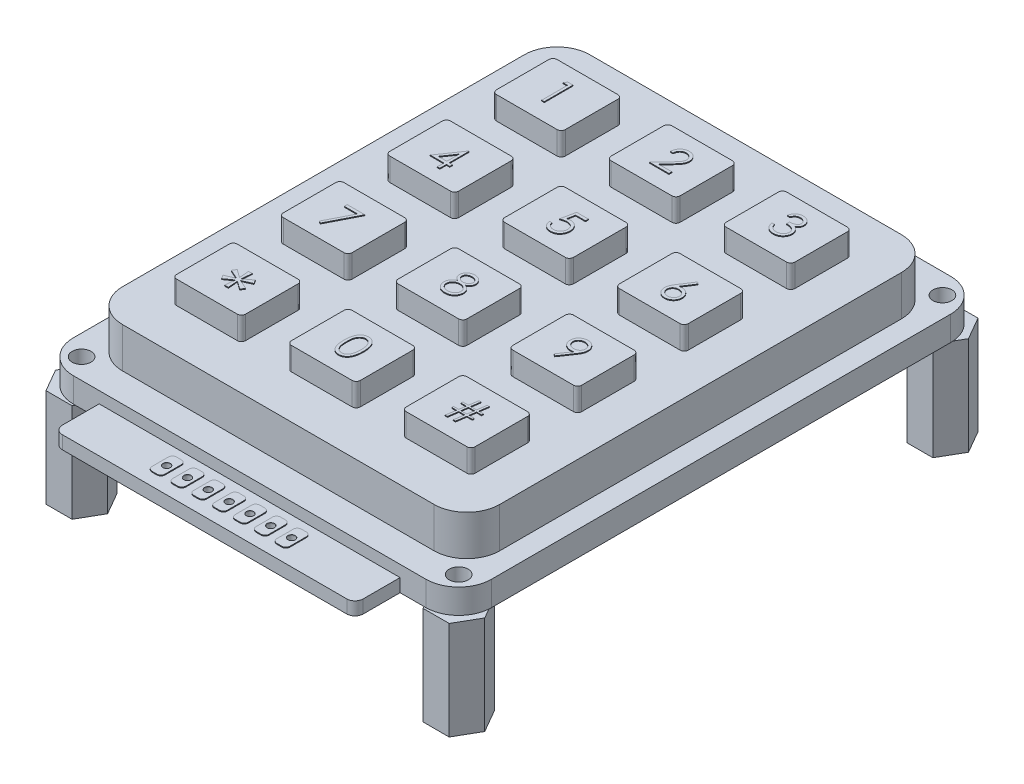
SolidWorks part; units mm, degrees
ref_plane "Front Plane" through (0, 0, 0) normal (0, 0, 1) x (1, 0, 0)
ref_plane "Top Plane" through (0, 0, 0) normal (0, 1, 0) x (1, 0, 0)
ref_plane "Right Plane" through (0, 0, 0) normal (1, 0, 0) x (0, 0, -1)
sketch "Sketch1" plane through (0, 0, 0) normal (0, 1, 0) x (1, 0, 0)
  line L0 (0, 71.2613) -> (0, -45.8043) construction
  line L1 (19.8246, -29.5) -> (21.4123, -32.25)
  line L2 (-19.8246, -29.5) -> (-21.4123, -26.75)
  line L3 (-21.4123, -26.75) -> (-24.5877, -26.75)
  line L4 (-24.5877, -26.75) -> (-26.1754, -29.5)
  line L5 (-26.1754, -29.5) -> (-24.5877, -32.25)
  line L6 (-24.5877, -32.25) -> (-21.4123, -32.25)
  line L7 (-21.4123, -32.25) -> (-19.8246, -29.5)
  line L8 (21.4123, -26.75) -> (19.8246, -29.5)
  line L9 (24.5877, -26.75) -> (21.4123, -26.75)
  line L10 (26.1754, -29.5) -> (24.5877, -26.75)
  line L11 (24.5877, -32.25) -> (26.1754, -29.5)
  line L12 (21.4123, -32.25) -> (24.5877, -32.25)
  line L13 (19.8246, 29.5) -> (21.4123, 26.75)
  line L14 (21.4123, 32.25) -> (19.8246, 29.5)
  line L15 (24.5877, 32.25) -> (21.4123, 32.25)
  line L16 (26.1754, 29.5) -> (24.5877, 32.25)
  line L17 (24.5877, 26.75) -> (26.1754, 29.5)
  line L18 (21.4123, 26.75) -> (24.5877, 26.75)
  line L19 (-26.1754, 29.5) -> (-24.5877, 26.75)
  line L20 (-24.5877, 32.25) -> (-26.1754, 29.5)
  line L21 (-21.4123, 32.25) -> (-24.5877, 32.25)
  line L22 (-19.8246, 29.5) -> (-21.4123, 32.25)
  line L23 (-21.4123, 26.75) -> (-19.8246, 29.5)
  line L24 (-24.5877, 26.75) -> (-21.4123, 26.75)
  circle A0 centre (-23, -29.5) radius 2.75 construction
  circle A1 centre (-23, -29.5) radius 1.5
  circle A2 centre (23, -29.5) radius 1.5
  circle A3 centre (23, 29.5) radius 1.5
  circle A4 centre (-23, 29.5) radius 1.5
  point P41 (0, 0)
  dimension "D1" = 29.5
  dimension "D3" = 2.75
  dimension "D4" = 3
  dimension "D10" = 29.5
  dimension "D11" = 23
  dimension "D5" = 5.5
  dimension "D2" = 23
  dimension "D6" = 2
  dimension "D7" = 2
  dimension "D8" = 29.5
  dimension "D9" = 46
extrude "Boss-Extrude1" add sketch "Sketch1" along normal blind 12
sketch "Sketch3" plane through (0, 12, 0) normal (0, 1, 0) x (1, 0, 0)
  line L1 (-21.5, -32) -> (21.5, -32)
  line L2 (-25.5, -28) -> (-25.5, 28)
  line L3 (-21.5, 32) -> (21.5, 32)
  line L4 (25.5, -28) -> (25.5, 28)
  line L5 (-25.5, -32) -> (25.5, 32) construction
  line L6 (-25.5, 32) -> (25.5, -32) construction
  circle A0 centre (-23, 29.5) radius 1.15
  circle A1 centre (23, 29.5) radius 1.15
  circle A2 centre (23, -29.5) radius 1.15
  circle A3 centre (-23, -29.5) radius 1.15
  arc A4 (-25.5, 28) -> (-21.5, 32) centre (-21.5, 28) cw
  arc A5 (21.5, 32) -> (25.5, 28) centre (21.5, 28) cw
  arc A6 (21.5, -32) -> (25.5, -28) centre (21.5, -28) ccw
  arc A7 (-21.5, -32) -> (-25.5, -28) centre (-21.5, -28) cw
  point P0 (0, 0)
  dimension "D3" = 2.3
  dimension "D10" = 4
  dimension "D11" = 4
  dimension "D12" = 4
  dimension "D13" = 4
  dimension "D1" = 64
  dimension "D2" = 51
  dimension "D6" = 46
  dimension "D7" = 59
  dimension "D8" = 29.5
  dimension "D9" = 23
  dimension "D4" = 2
  dimension "D5" = 2
extrude "Boss-Extrude3" add sketch "Sketch3" along normal blind 3 separate body
sketch "Sketch6" plane through (0, 15, 0) normal (0, 1, 0) x (1, 0, 0)
  line L1 (-19, -28.5) -> (19, -28.5)
  line L2 (-23, -24.5) -> (-23, 24.5)
  line L3 (-19, 28.5) -> (19, 28.5)
  line L4 (23, -24.5) -> (23, 24.5)
  line L5 (-23, -28.5) -> (23, 28.5) construction
  line L6 (-23, 28.5) -> (23, -28.5) construction
  arc A0 (-23, 24.5) -> (-19, 28.5) centre (-19, 24.5) cw
  arc A1 (-19, -28.5) -> (-23, -24.5) centre (-19, -24.5) cw
  arc A2 (19, -28.5) -> (23, -24.5) centre (19, -24.5) ccw
  arc A3 (19, 28.5) -> (23, 24.5) centre (19, 24.5) cw
  point P0 (0, 0)
  dimension "D3" = 4
  dimension "D4" = 4
  dimension "D5" = 4
  dimension "D6" = 4
  dimension "D1" = 57
  dimension "D2" = 46
extrude "Boss-Extrude4" add sketch "Sketch6" along normal blind 4.9 separate body
sketch "Sketch7" plane through (0, 19.9, 0) normal (0, 1, 0) x (1, 0, 0)
  line L0 (-3.7, -15.8) -> (3.7, -15.8)
  line L1 (-17.7, -23.2) -> (-10.3, -23.2)
  line L2 (-18.2, -22.7) -> (-18.2, -16.3)
  line L3 (-17.7, -15.8) -> (-10.3, -15.8)
  line L4 (-9.8, -22.7) -> (-9.8, -16.3)
  line L5 (-18.2, -23.2) -> (-9.8, -15.8) construction
  line L6 (-18.2, -15.8) -> (-9.8, -23.2) construction
  line L7 (-4.2, -22.7) -> (-4.2, -16.3)
  line L8 (-3.7, -23.2) -> (3.7, -23.2)
  line L9 (4.2, -22.7) -> (4.2, -16.3)
  line L10 (10.3, -15.8) -> (17.7, -15.8)
  line L11 (9.8, -22.7) -> (9.8, -16.3)
  line L12 (10.3, -23.2) -> (17.7, -23.2)
  line L13 (18.2, -22.7) -> (18.2, -16.3)
  line L14 (-3.7, -2.8) -> (3.7, -2.8)
  line L15 (-4.2, -9.7) -> (-4.2, -3.3)
  line L16 (-3.7, -10.2) -> (3.7, -10.2)
  line L17 (4.2, -9.7) -> (4.2, -3.3)
  line L18 (10.3, -2.8) -> (17.7, -2.8)
  line L19 (9.8, -9.7) -> (9.8, -3.3)
  line L20 (10.3, -10.2) -> (17.7, -10.2)
  line L21 (18.2, -9.7) -> (18.2, -3.3)
  line L22 (-3.7, 10.2) -> (3.7, 10.2)
  line L23 (-4.2, 3.3) -> (-4.2, 9.7)
  line L24 (-3.7, 2.8) -> (3.7, 2.8)
  line L25 (4.2, 3.3) -> (4.2, 9.7)
  line L26 (10.3, 10.2) -> (17.7, 10.2)
  line L27 (9.8, 3.3) -> (9.8, 9.7)
  line L28 (10.3, 2.8) -> (17.7, 2.8)
  line L29 (18.2, 3.3) -> (18.2, 9.7)
  line L30 (-3.7, 23.2) -> (3.7, 23.2)
  line L31 (-4.2, 16.3) -> (-4.2, 22.7)
  line L32 (-3.7, 15.8) -> (3.7, 15.8)
  line L33 (4.2, 16.3) -> (4.2, 22.7)
  line L34 (10.3, 23.2) -> (17.7, 23.2)
  line L35 (9.8, 16.3) -> (9.8, 22.7)
  line L36 (10.3, 15.8) -> (17.7, 15.8)
  line L37 (18.2, 16.3) -> (18.2, 22.7)
  line L38 (-17.7, -2.8) -> (-10.3, -2.8)
  line L39 (-18.2, -9.7) -> (-18.2, -3.3)
  line L40 (-17.7, -10.2) -> (-10.3, -10.2)
  line L41 (-9.8, -9.7) -> (-9.8, -3.3)
  line L42 (-17.7, 10.2) -> (-10.3, 10.2)
  line L43 (-18.2, 3.3) -> (-18.2, 9.7)
  line L44 (-17.7, 2.8) -> (-10.3, 2.8)
  line L45 (-9.8, 3.3) -> (-9.8, 9.7)
  line L46 (-17.7, 23.2) -> (-10.3, 23.2)
  line L47 (-18.2, 16.3) -> (-18.2, 22.7)
  line L48 (-17.7, 15.8) -> (-10.3, 15.8)
  line L49 (-9.8, 16.3) -> (-9.8, 22.7)
  arc A0 (-10.3, -23.2) -> (-9.8, -22.7) centre (-10.3, -22.7) ccw
  arc A1 (-10.3, -15.8) -> (-9.8, -16.3) centre (-10.3, -16.3) cw
  arc A2 (-18.2, -16.3) -> (-17.7, -15.8) centre (-17.7, -16.3) cw
  arc A3 (-17.7, -23.2) -> (-18.2, -22.7) centre (-17.7, -22.7) cw
  arc A4 (9.8, 16.3) -> (10.3, 15.8) centre (10.3, 16.3) ccw
  arc A5 (17.7, 15.8) -> (18.2, 16.3) centre (17.7, 16.3) ccw
  arc A6 (17.7, 23.2) -> (18.2, 22.7) centre (17.7, 22.7) cw
  arc A7 (10.3, 23.2) -> (9.8, 22.7) centre (10.3, 22.7) ccw
  arc A8 (-4.2, 16.3) -> (-3.7, 15.8) centre (-3.7, 16.3) ccw
  arc A9 (3.7, 15.8) -> (4.2, 16.3) centre (3.7, 16.3) ccw
  arc A10 (3.7, 23.2) -> (4.2, 22.7) centre (3.7, 22.7) cw
  arc A11 (-3.7, 23.2) -> (-4.2, 22.7) centre (-3.7, 22.7) ccw
  arc A12 (-18.2, 16.3) -> (-17.7, 15.8) centre (-17.7, 16.3) ccw
  arc A13 (-10.3, 15.8) -> (-9.8, 16.3) centre (-10.3, 16.3) ccw
  arc A14 (-10.3, 23.2) -> (-9.8, 22.7) centre (-10.3, 22.7) cw
  arc A15 (-17.7, 23.2) -> (-18.2, 22.7) centre (-17.7, 22.7) ccw
  arc A16 (-18.2, 3.3) -> (-17.7, 2.8) centre (-17.7, 3.3) ccw
  arc A17 (-10.3, 2.8) -> (-9.8, 3.3) centre (-10.3, 3.3) ccw
  arc A18 (-10.3, 10.2) -> (-9.8, 9.7) centre (-10.3, 9.7) cw
  arc A19 (-17.7, 10.2) -> (-18.2, 9.7) centre (-17.7, 9.7) ccw
  arc A20 (-4.2, 3.3) -> (-3.7, 2.8) centre (-3.7, 3.3) ccw
  arc A21 (3.7, 2.8) -> (4.2, 3.3) centre (3.7, 3.3) ccw
  arc A22 (3.7, 10.2) -> (4.2, 9.7) centre (3.7, 9.7) cw
  arc A23 (-3.7, 10.2) -> (-4.2, 9.7) centre (-3.7, 9.7) ccw
  arc A24 (17.7, 10.2) -> (18.2, 9.7) centre (17.7, 9.7) cw
  arc A25 (10.3, 10.2) -> (9.8, 9.7) centre (10.3, 9.7) ccw
  arc A26 (9.8, 3.3) -> (10.3, 2.8) centre (10.3, 3.3) ccw
  arc A27 (17.7, 2.8) -> (18.2, 3.3) centre (17.7, 3.3) ccw
  arc A28 (-17.7, -2.8) -> (-18.2, -3.3) centre (-17.7, -3.3) ccw
  arc A29 (-18.2, -9.7) -> (-17.7, -10.2) centre (-17.7, -9.7) ccw
  arc A30 (-10.3, -10.2) -> (-9.8, -9.7) centre (-10.3, -9.7) ccw
  arc A31 (-10.3, -2.8) -> (-9.8, -3.3) centre (-10.3, -3.3) cw
  arc A32 (-3.7, -2.8) -> (-4.2, -3.3) centre (-3.7, -3.3) ccw
  arc A33 (-4.2, -9.7) -> (-3.7, -10.2) centre (-3.7, -9.7) ccw
  arc A34 (3.7, -10.2) -> (4.2, -9.7) centre (3.7, -9.7) ccw
  arc A35 (3.7, -2.8) -> (4.2, -3.3) centre (3.7, -3.3) cw
  arc A36 (10.3, -2.8) -> (9.8, -3.3) centre (10.3, -3.3) ccw
  arc A37 (9.8, -9.7) -> (10.3, -10.2) centre (10.3, -9.7) ccw
  arc A38 (17.7, -10.2) -> (18.2, -9.7) centre (17.7, -9.7) ccw
  arc A39 (17.7, -2.8) -> (18.2, -3.3) centre (17.7, -3.3) cw
  arc A40 (9.8, -22.7) -> (10.3, -23.2) centre (10.3, -22.7) ccw
  arc A41 (17.7, -23.2) -> (18.2, -22.7) centre (17.7, -22.7) ccw
  arc A42 (17.7, -15.8) -> (18.2, -16.3) centre (17.7, -16.3) cw
  arc A43 (10.3, -15.8) -> (9.8, -16.3) centre (10.3, -16.3) ccw
  arc A44 (3.7, -23.2) -> (4.2, -22.7) centre (3.7, -22.7) ccw
  arc A45 (3.7, -15.8) -> (4.2, -16.3) centre (3.7, -16.3) cw
  arc A46 (-3.7, -15.8) -> (-4.2, -16.3) centre (-3.7, -16.3) ccw
  arc A47 (-4.2, -22.7) -> (-3.7, -23.2) centre (-3.7, -22.7) ccw
  point P0 (-14, -19.5)
  dimension "D7" = 0.5
  dimension "D8" = 0.5
  dimension "D1" = 7.4
  dimension "D2" = 8.4
  dimension "D3" = 19.5
  dimension "D4" = 14
  dimension "D5" = 3
  dimension "D6" = 4
extrude "Boss-Extrude5" add sketch "Sketch7" along normal blind 2.8 separate body
sketch "Sketch9" plane through (0, 22.7, 0) normal (0, 1, 0) x (1, 0, 0)
  text T0 "1"
  text T1 "2"
  text T2 "3"
  text T3 "4"
  text T4 "5"
  text T5 "6"
  text T6 "7"
  text T7 "8"
  text T8 "9"
  text T9 "*" font "Century Gothic" height 6
  text T10 "#"
  text T11 "0"
extrude "Boss-Extrude6" add sketch "Sketch9" along normal blind 0.1 separate body
sketch "Sketch12" plane through (0, 12, 0) normal (0, 1, 0) x (1, 0, 0)
  line L1 (-21.5, -32) -> (21.5, -32) construction
  line L2 (-18.35, -37.5) -> (18.35, -37.5)
  line L3 (-18.35, -37.5) -> (-18.35, -32)
  line L4 (-18.35, -32) -> (18.35, -32)
  line L5 (18.35, -37.5) -> (18.35, -32)
  line L6 (-18.35, -37.5) -> (18.35, -32) construction
  line L7 (-18.35, -32) -> (18.35, -37.5) construction
  line L8 (0, 0) -> (0, -66.9703) construction
  point P0 (0, -34.75)
  dimension "D1" = 5.5
  dimension "D2" = 36.7
extrude "Boss-Extrude7" add sketch "Sketch12" along normal blind 1.6 separate body
sketch "Sketch15" plane through (0, 13.6, 0) normal (0, 1, 0) x (1, 0, 0)
  line L0 (-20, -34.5) -> (20, -34.5) construction
  line L1 (1.74, -35.5) -> (1.74, -33.5)
  line L2 (-0.3, -36) -> (0.3, -36)
  line L3 (-0.8, -35.5) -> (-0.8, -33.5)
  line L4 (-0.3, -33) -> (0.3, -33)
  line L5 (0.8, -35.5) -> (0.8, -33.5)
  line L6 (-0.8, -36) -> (0.8, -33) construction
  line L7 (-0.8, -33) -> (0.8, -36) construction
  line L8 (2.24, -33) -> (2.84, -33)
  line L9 (3.34, -35.5) -> (3.34, -33.5)
  line L10 (2.24, -36) -> (2.84, -36)
  line L11 (4.28, -35.5) -> (4.28, -33.5)
  line L12 (4.78, -33) -> (5.38, -33)
  line L13 (5.88, -35.5) -> (5.88, -33.5)
  line L14 (4.78, -36) -> (5.38, -36)
  line L15 (6.82, -35.5) -> (6.82, -33.5)
  line L16 (7.32, -33) -> (7.92, -33)
  line L17 (8.42, -35.5) -> (8.42, -33.5)
  line L18 (7.32, -36) -> (7.92, -36)
  line L19 (-3.34, -35.5) -> (-3.34, -33.5)
  line L20 (-2.84, -33) -> (-2.24, -33)
  line L21 (-1.74, -35.5) -> (-1.74, -33.5)
  line L22 (-2.84, -36) -> (-2.24, -36)
  line L23 (-5.88, -35.5) -> (-5.88, -33.5)
  line L24 (-5.38, -33) -> (-4.78, -33)
  line L25 (-4.28, -35.5) -> (-4.28, -33.5)
  line L26 (-5.38, -36) -> (-4.78, -36)
  line L27 (-8.42, -35.5) -> (-8.42, -33.5)
  line L28 (-7.92, -33) -> (-7.32, -33)
  line L29 (-6.82, -35.5) -> (-6.82, -33.5)
  line L30 (-7.92, -36) -> (-7.32, -36)
  arc A0 (-0.3, -36) -> (-0.8, -35.5) centre (-0.3, -35.5) cw
  arc A1 (0.3, -36) -> (0.8, -35.5) centre (0.3, -35.5) ccw
  arc A2 (0.3, -33) -> (0.8, -33.5) centre (0.3, -33.5) cw
  arc A3 (-0.8, -33.5) -> (-0.3, -33) centre (-0.3, -33.5) cw
  arc A4 (1.74, -33.5) -> (2.24, -33) centre (2.24, -33.5) cw
  arc A5 (2.84, -33) -> (3.34, -33.5) centre (2.84, -33.5) cw
  arc A6 (2.84, -36) -> (3.34, -35.5) centre (2.84, -35.5) ccw
  arc A7 (2.24, -36) -> (1.74, -35.5) centre (2.24, -35.5) cw
  arc A8 (4.28, -33.5) -> (4.78, -33) centre (4.78, -33.5) cw
  arc A9 (5.38, -33) -> (5.88, -33.5) centre (5.38, -33.5) cw
  arc A10 (5.38, -36) -> (5.88, -35.5) centre (5.38, -35.5) ccw
  arc A11 (4.78, -36) -> (4.28, -35.5) centre (4.78, -35.5) cw
  arc A12 (6.82, -33.5) -> (7.32, -33) centre (7.32, -33.5) cw
  arc A13 (7.92, -33) -> (8.42, -33.5) centre (7.92, -33.5) cw
  arc A14 (7.92, -36) -> (8.42, -35.5) centre (7.92, -35.5) ccw
  arc A15 (7.32, -36) -> (6.82, -35.5) centre (7.32, -35.5) cw
  arc A16 (-3.34, -33.5) -> (-2.84, -33) centre (-2.84, -33.5) cw
  arc A17 (-2.24, -33) -> (-1.74, -33.5) centre (-2.24, -33.5) cw
  arc A18 (-2.24, -36) -> (-1.74, -35.5) centre (-2.24, -35.5) ccw
  arc A19 (-2.84, -36) -> (-3.34, -35.5) centre (-2.84, -35.5) cw
  arc A20 (-5.88, -33.5) -> (-5.38, -33) centre (-5.38, -33.5) cw
  arc A21 (-4.78, -33) -> (-4.28, -33.5) centre (-4.78, -33.5) cw
  arc A22 (-4.78, -36) -> (-4.28, -35.5) centre (-4.78, -35.5) ccw
  arc A23 (-5.38, -36) -> (-5.88, -35.5) centre (-5.38, -35.5) cw
  arc A24 (-8.42, -33.5) -> (-7.92, -33) centre (-7.92, -33.5) cw
  arc A25 (-7.32, -33) -> (-6.82, -33.5) centre (-7.32, -33.5) cw
  arc A26 (-7.32, -36) -> (-6.82, -35.5) centre (-7.32, -35.5) ccw
  arc A27 (-7.92, -36) -> (-8.42, -35.5) centre (-7.92, -35.5) cw
  point P2 (0, -34.5)
  dimension "D3" = 0.5
  dimension "D1" = 3
  dimension "D2" = 1.6
  dimension "D4" = 4
  dimension "D5" = 4
extrude "Boss-Extrude9" add sketch "Sketch15" along normal blind 0.1 separate body
sketch "Sketch16" plane through (0, 13.7, 0) normal (0, 1, 0) x (1, 0, 0)
  circle A0 centre (0, -34.5) radius 0.45
  circle A1 centre (2.54, -34.5) radius 0.45
  circle A2 centre (5.08, -34.5) radius 0.45
  circle A3 centre (7.62, -34.5) radius 0.45
  circle A4 centre (-2.54, -34.5) radius 0.45
  circle A5 centre (-5.08, -34.5) radius 0.45
  circle A6 centre (-7.62, -34.5) radius 0.45
  dimension "D1" = 4
  dimension "D2" = 4
extrude "Cut-Extrude1" cut sketch "Sketch16" against normal up to surface (1.7 mm away) up to face at (0, 12, 34.75)
fillet "Fillet1" radius 1 2 edges at (-18.35, 12.8, 37.5) (18.35, 12.8, 37.5)
